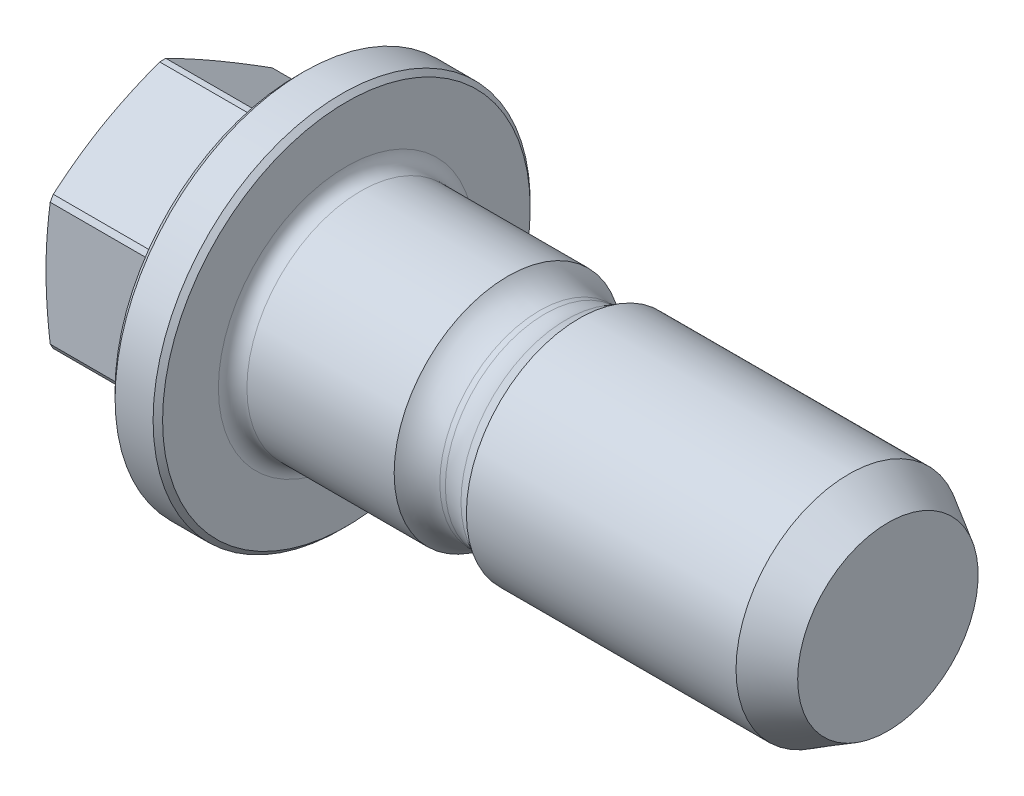
SolidWorks part; units mm, degrees
material "4340 H/T-Y"
ref_plane "Front Plane" through (0, 0, 0) normal (0, 0, 1) x (1, 0, 0)
ref_plane "Top Plane" through (0, 0, 0) normal (0, 1, 0) x (1, 0, 0)
ref_plane "Right Plane" through (0, 0, 0) normal (1, 0, 0) x (0, 0, -1)
sketch "Sketch1" plane through (0, 0, 0) normal (0, 1, 0) x (1, 0, 0)
  line L0 (0, 0) -> (108.2734, 0) construction
  line L1 (20, 13.475) -> (20, 19.85)
  line L2 (21.5, 11.975) -> (37, 11.975)
  line L3 (20, 19.85) -> (15, 19.85)
  line L4 (40.9127, 10.5) -> (40.3316, 10.5)
  line L5 (77, 9.5) -> (77, 0)
  line L6 (15, 19.85) -> (13, 13.5)
  line L7 (13, 13.5) -> (0.6699, 13.5)
  line L8 (0, 11) -> (0, 0)
  line L9 (0, 0) -> (77, 0)
  line L10 (0, 11) -> (0.6699, 13.5)
  line L11 (72.8864, 11.875) -> (77, 9.5)
  line L14 (43.1627, 11.1029) -> (44.5, 11.875)
  line L15 (44.5, 11.875) -> (72.8864, 11.875)
  arc A0 (40.9127, 10.5) -> (43.1627, 11.1029) centre (40.9127, 15) ccw
  arc A1 (21.5, 11.975) -> (20, 13.475) centre (21.5, 13.475) cw
  arc A2 (37, 11.975) -> (40.3316, 10.5) centre (40.3316, 15) ccw
  dimension "D9" = 19
  dimension "D10" = 1.5
  dimension "D15" = 30
  dimension "D16" = 21
  dimension "D18" = 4.5
  dimension "D6" = 4.5
  dimension "D1" = 27
  dimension "D2" = 30
  dimension "D3" = 57
  dimension "D4" = 23.95
  dimension "D5" = 2
  dimension "D7" = 39.7
  dimension "D8" = 77
  dimension "D11" = 15
  dimension "D12" = 22
  dimension "D13" = 40
  dimension "D14" = 23.75
  dimension "D17" = 32.5
  dimension "D19" = 13
revolve "Revolve1" add sketch "Sketch1" angle 360 about L0
cosmetic thread "Cosmetic Thread2" parameters "D1"=33.5, "D2"=21
sketch "Sketch5" plane through (0, 0, 0) normal (-1, 0, 0) x (0, 0, 1)
  line L1 (0, 13.6832) -> (-11.85, 6.8416)
  line L2 (-11.85, 6.8416) -> (-11.85, -6.8416)
  line L3 (-11.85, -6.8416) -> (0, -13.6832)
  line L4 (0, -13.6832) -> (11.85, -6.8416)
  line L5 (11.85, -6.8416) -> (11.85, 6.8416)
  line L6 (11.85, 6.8416) -> (0, 13.6832)
  circle A0 centre (0, 0) radius 13.6832 construction
  dimension "D1" = 23.7
chamfer "Chamfer1" distance 0.5 angle 45 2 edges at (20, 0, 19.85) (15, 0, 19.85) first distance on face at (20, 0, 19.85) first distance on face at (15, 0, 19.85)
extrude "Cut-Extrude2" cut sketch "Sketch5" against normal blind 13 flip side to cut
fillet "Fillet2" radius 1 6 edges at (13, 10.2624, -5.925) (13, 0, -11.85) (13, -10.2624, -5.925) (13, -10.2624, 5.925) (13, 0, 11.85) (13, 10.2624, 5.925)
sketch "Sketch6" plane through (0, 0, 0) normal (-1, 0, 0) x (0, 0, 1)
  line L0 (-8.9896, 0.9178) -> (9.5, 0.9178) construction
  text T0 "550 034 00\r\n11111-XX - M" font "Century Gothic" height 1.8
extrude "Cut-Extrude3" cut sketch "Sketch6" against normal blind 0.01
sketch "Sketch7" [suppressed] plane through (0, 0, 0) normal (0, 1, 0) x (1, 0, 0)
  line L0 (0, 0) -> (-17.8371, 0) construction
  line L1 (40.3316, 10.975) -> (77, 10.975)
  line L2 (77, 10.975) -> (77, 12.5)
  line L3 (40.3316, -10.5) -> (40.3316, 10.5) construction
  line L4 (40.3316, 10.975) -> (40.3316, 12.5)
  line L5 (40.3316, 12.5) -> (77, 12.5)
  line L6 (77, 9.5) -> (77, 0) construction
  dimension "D1" = 21.95
  dimension "D2" = 25
revolve "Cut-Revolve1" [suppressed] cut sketch "Sketch7" angle 360 about L0
